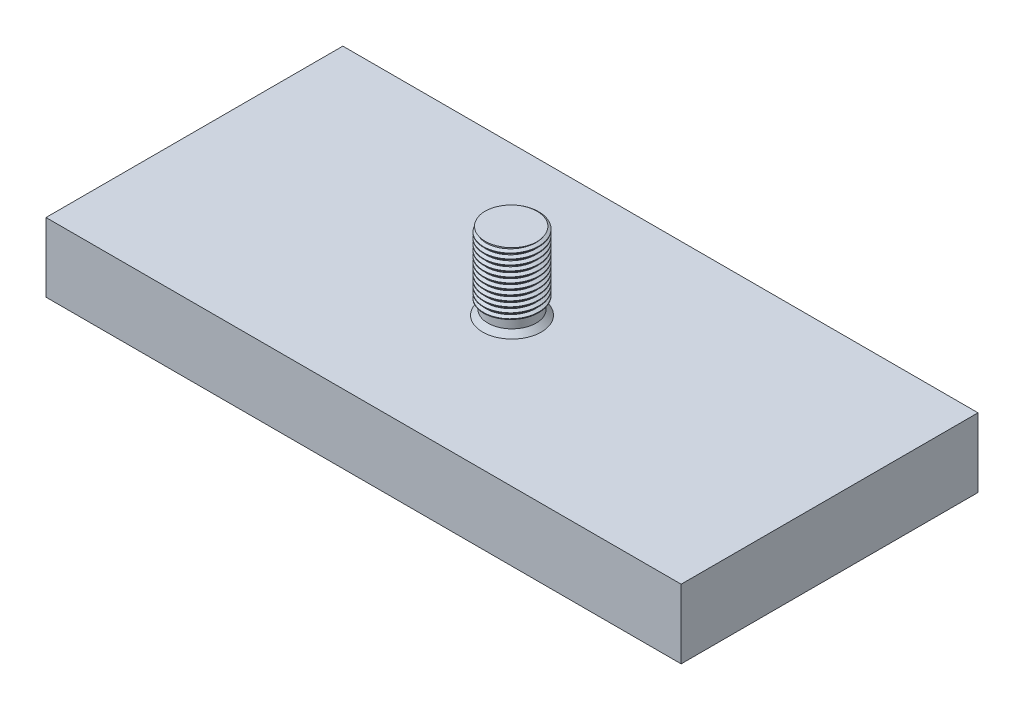
SolidWorks part; units mm, degrees
ref_plane "Front Plane" through (0, 0, 0) normal (0, 0, 1) x (1, 0, 0)
ref_plane "Top Plane" through (0, 0, 0) normal (0, 1, 0) x (1, 0, 0)
ref_plane "Right Plane" through (0, 0, 0) normal (1, 0, 0) x (0, 0, -1)
sketch "Sketch1" plane through (0, 0, 0) normal (0, 1, 0) x (1, 0, 0)
  line L1 (92, 43) -> (-92, 43)
  line L2 (92, 43) -> (92, -43)
  line L3 (92, -43) -> (-92, -43)
  line L4 (-92, 43) -> (-92, -43)
  line L5 (92, 43) -> (-92, -43) construction
  line L6 (92, -43) -> (-92, 43) construction
  point P0 (0, 0)
  dimension "D1" = 184
  dimension "D2" = 86
extrude "plate" add sketch "Sketch1" along normal blind 20
sketch "Sketch2" plane through (0, 20, 0) normal (0, 1, 0) x (1, 0, 0)
  circle A0 centre (0, 0) radius 7
  dimension "D1" = 14
extrude "neck" add sketch "Sketch2" along normal blind 4
sketch "Sketch3" plane through (0, 24, 0) normal (0, 1, 0) x (1, 0, 0)
  circle A0 centre (0, 0) radius 8
  dimension "D1" = 16
extrude "bolt" add sketch "Sketch3" along normal blind 18
thread "m16 thread" pitch 1.5 method cut profile "Thread Profile1" start angle 0, offset 1.5, length 0, pitch 1.5, diameter 16
ref_plane "Plane1" through (-8, 43.5, 0) normal (0, 0, 1) x (-1, 0, 0)
sketch "Thread Profile1" plane through (-8, 43.5, 0) normal (0, 0, 1) x (-1, 0, 0)
  line L0 (0, 0) -> (0, 1.5) construction
  line L11 (0, 0) -> (0, 1.3125)
  line L12 (0, 1.3125) -> (-0.8119, 0.8437)
  line L13 (-0.8119, 0.8437) -> (-0.8119, 0.4687)
  line L15 (-0.8119, 0.4687) -> (0, 0)
  line L17 (-0.8119, 0.6562) -> (0, 0.6562) construction
  point P2 (0, 0)
  dimension "Pitch" = 1.5
  dimension "Profile_Angle" = 60
  dimension "Profile_Land" = 0.375
  dimension "Profile_Height" = 0.8119
chamfer "weldingCorner" distance 1.5 angle 45 1 edges at (0, 20, -7)
equation "\"D1@Sketch1\"=144+40"
equation "\"D2@Sketch1\"=46+40"
